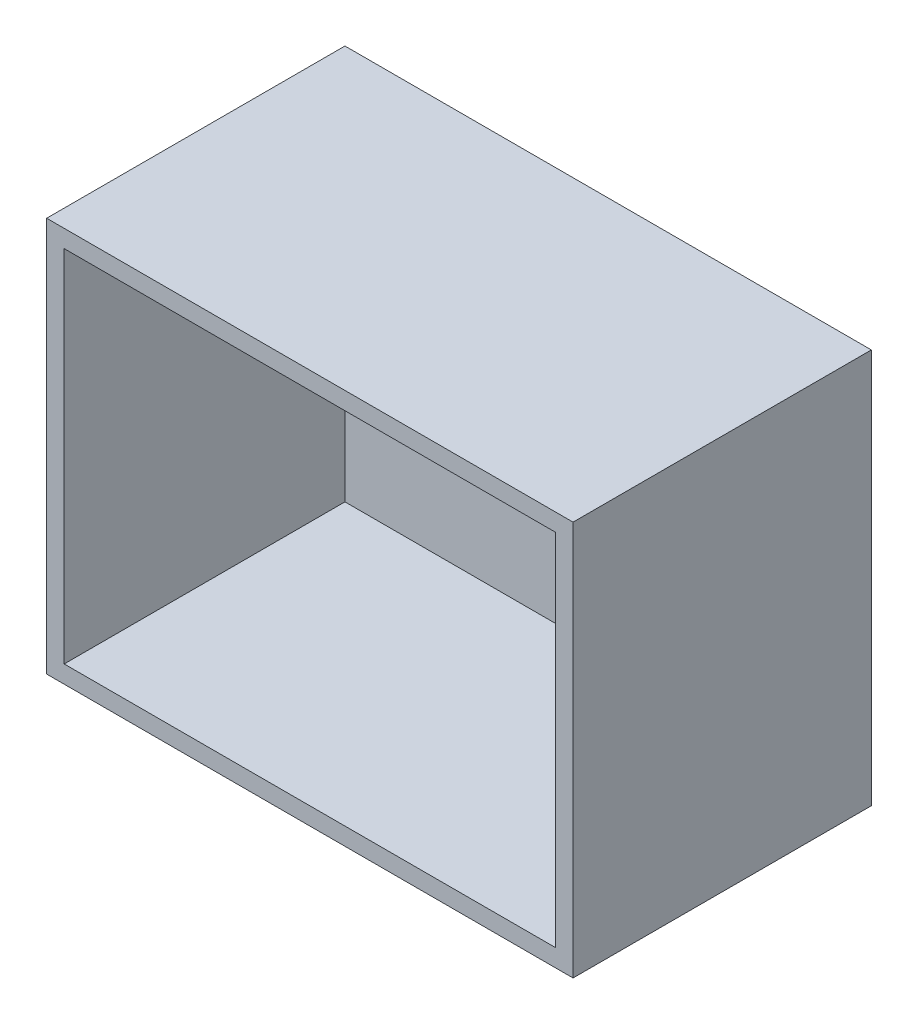
SolidWorks part; units mm, degrees
material "ABS"
ref_plane "Front Plane" through (0, 0, 0) normal (0, 0, 1) x (1, 0, 0)
ref_plane "Top Plane" through (0, 0, 0) normal (0, 1, 0) x (1, 0, 0)
ref_plane "Right Plane" through (0, 0, 0) normal (1, 0, 0) x (0, 0, -1)
sketch "Sketch1" plane through (0, 0, 0) normal (0, 1, 0) x (1, 0, 0)
  line L1 (0, 0) -> (-300, 0)
  line L2 (0, 0) -> (0, -170)
  line L3 (0, -170) -> (-300, -170)
  line L4 (-300, 0) -> (-300, -170)
  dimension "D1" = 300
  dimension "D2" = 170
extrude "Boss-Extrude1" add sketch "Sketch1" along normal blind 225
shell "Shell1" thickness 10 removed face at (-150, 112.5, 170)
sketch "Sketch2" plane through (0, 0, 10) normal (0, 0, 1) x (1, 0, 0)
  line L0 (-290, 112.5) -> (-10, 112.5) construction
  line L1 (-290, 215) -> (-290, 10) construction
  line L2 (-10, 215) -> (-10, 10) construction
  circle A0 centre (-260, 112.5) radius 6.5
  dimension "D1" = 13
  dimension "D2" = 30
extrude "Cut-Extrude1" cut sketch "Sketch2" against normal blind 10
sketch "Sketch3" plane through (0, 0, 10) normal (0, 0, 1) x (1, 0, 0)
  line L0 (-260, 112.5) -> (-260, 135) construction
  line L1 (-260, 112.5) -> (-244.0901, 128.4099) construction
  circle A0 centre (-260, 112.5) radius 22.5 construction
  dimension "D1" = 45
  dimension "D2" = 45
hole_wizard "M5 Clearance Hole1" positions "Sketch4" profile "Sketch5" hole size "M5" standard "ANSI Metric"
sketch "Sketch4" plane through (0, 0, 10) normal (0, 0, 1) x (1, 0, 0)
  point P0 (-244.0901, 128.4099)
sketch "Sketch5" plane through (-244.0901, 128.4099, 10) normal (1, 0, 0) x (0, -1, 0)
  line L0 (0, 0) -> (0, 21.6524)
  line L1 (0, 21.6524) -> (2.75, 20)
  line L2 (2.75, 20) -> (2.75, 0.025)
  line L3 (2.75, 0.025) -> (2.775, 0)
  line L5 (2.775, 0) -> (0, 0)
  line L6 (-2.75, 0.025) -> (-2.775, 0) construction
  line L10 (0, 21.6524) -> (-2.75, 20) construction
  line L11 (0, -6.35) -> (0, 107.95) construction
  dimension "Hole Dia." = 5.5
  dimension "Hole Depth" = 20
  dimension "Near C'Sink Dia." = 5.55
  dimension "Near C'Sink Angle" = 90
  dimension "Drill Angle" = 118
pattern_circular "CirPattern1" count 4 over 360 about axis through (-260, 112.5, 10) along (0, 0, 1) of "M5 Clearance Hole1"
sketch "Sketch6" plane through (0, 0, 10) normal (0, 0, 1) x (1, 0, 0)
  line L0 (-150, 215) -> (-150, 10) construction
  line L1 (-10, 215) -> (-290, 215) construction
  line L2 (-10, 10) -> (-290, 10) construction
  line L4 (-182, 80.5) -> (-118, 80.5) construction
  line L5 (-182, 80.5) -> (-182, 144.5) construction
  line L6 (-182, 144.5) -> (-118, 144.5) construction
  line L7 (-118, 80.5) -> (-118, 144.5) construction
  line L8 (-182, 80.5) -> (-118, 144.5) construction
  line L9 (-182, 144.5) -> (-118, 80.5) construction
  circle A0 centre (-150, 112.5) radius 6
  circle A1 centre (-182, 144.5) radius 6
  circle A2 centre (-118, 144.5) radius 6
  circle A3 centre (-118, 80.5) radius 6
  circle A4 centre (-182, 80.5) radius 6
  point P12 (-118, 112.5)
  dimension "D1" = 12
  dimension "D4" = 12
  dimension "D2" = 64
  dimension "D3" = 64
extrude "Cut-Extrude2" cut sketch "Sketch6" against normal through all
